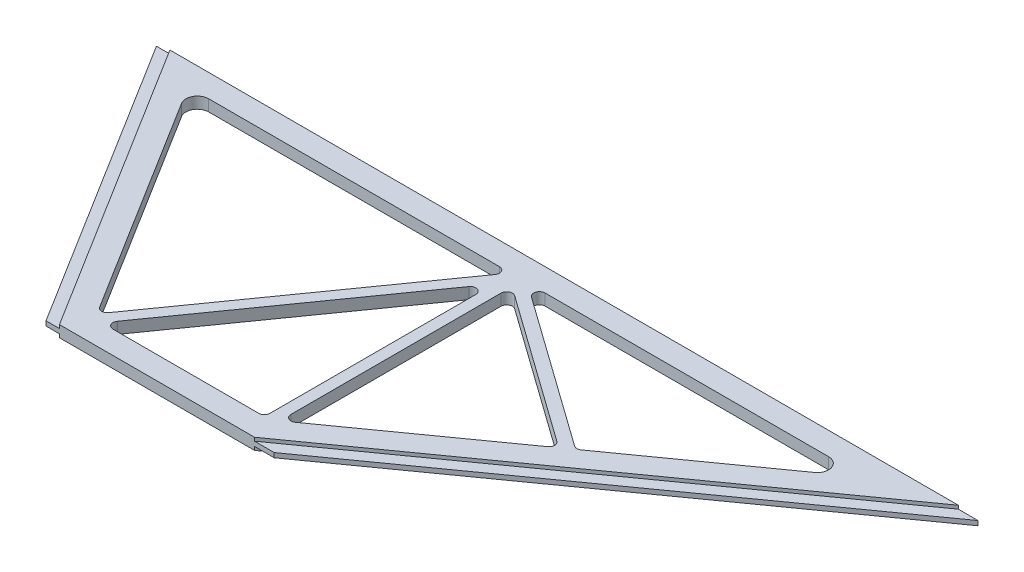
SolidWorks part; units mm, degrees
material "6061-T6 (SS)"
ref_plane "Front Plane" through (0, 0, 0) normal (0, 0, 1) x (1, 0, 0)
ref_plane "Top Plane" through (0, 0, 0) normal (0, 1, 0) x (1, 0, 0)
ref_plane "Right Plane" through (0, 0, 0) normal (1, 0, 0) x (0, 0, -1)
sketch "CS path" plane through (0, 0, 0) normal (0, 1, 0) x (1, 0, 0)
  line L0 (-228.6, 0) -> (228.6, 0)
  line L1 (0, 0) -> (-63.5, -163.068) construction
  line L2 (0, -163.068) -> (228.6, 0)
  line L6 (-127, -163.068) -> (0, -163.068)
  line L9 (-127, -163.068) -> (-228.6, 0) construction
  line L12 (-127, -163.068) -> (-228.6, 0)
  dimension "D1" = 457.2
  dimension "D2" = 127
  dimension "D3" = 163.068
  dimension "D4" = 228.6
extrude "Boss-Extrude1" add sketch "CS path" along normal blind 3.175 and the other way blind 3.175
sketch "Sketch1" plane through (0, 3.175, 0) normal (0, 1, 0) x (1, 0, 0)
  line L0 (-228.6, 0) -> (-127, -163.068)
  line L1 (0, -163.068) -> (228.6, 0)
  line L2 (-228.6, 0) -> (228.6, 0) construction
  line L3 (-127, -163.068) -> (0, -163.068) construction
  line L4 (-221.1183, 0) -> (-119.5183, -163.068)
  line L5 (-10.9346, -163.068) -> (217.6654, 0)
  line L6 (-223.2105, 3.3579) -> (-121.6105, -159.7101) construction
  line L7 (-3.6876, -157.8985) -> (224.9124, 5.1695) construction
  line L8 (-228.6, 0) -> (-221.1183, 0)
  line L9 (-127, -163.068) -> (-119.5183, -163.068)
  line L10 (0, -163.068) -> (-10.9346, -163.068)
  line L11 (217.6654, 0) -> (228.6, 0)
  dimension "D1" = 6.35
extrude "Cut-Extrude1" cut sketch "Sketch1" against normal blind 1.905
mirror "Mirror1" about plane through (0, 0, 0) normal (0, 1, 0) of "Cut-Extrude1"
sketch "Sketch2" plane through (0, 3.175, 0) normal (0, 1, 0) x (1, 0, 0)
  line L0 (-221.1183, 0) -> (217.6654, 0) construction
  line L1 (217.6654, 0) -> (-10.9346, -163.068) construction
  line L2 (-10.9346, -163.068) -> (-119.5183, -163.068) construction
  line L3 (-119.5183, -163.068) -> (-221.1183, 0) construction
  line L4 (-198.2422, -12.7) -> (177.9924, -12.7)
  line L5 (177.9924, -12.7) -> (-15.0001, -150.368)
  line L6 (-15.0001, -150.368) -> (-112.4677, -150.368)
  line L7 (-112.4677, -150.368) -> (-198.2422, -12.7)
  line L8 (-15.0001, -150.368) -> (-15.0001, -12.7) construction
  line L9 (-15.0001, -12.7) -> (-112.4677, -150.368) construction
  line L10 (-15.0001, -12.7) -> (81.4962, -81.534) construction
  line L11 (-15.0001, -150.368) -> (-198.2422, -12.7) construction
  dimension "D1" = 12.7
extrude "Cut-Extrude2" cut sketch "Sketch2" against normal blind 6.35
sketch "Sketch3" plane through (0, 3.175, 0) normal (0, 1, 0) x (1, 0, 0)
  line L0 (-15.0001, -150.368) -> (-15.0001, -12.7) construction
  line L1 (177.9924, -12.7) -> (-198.2422, -12.7) construction
  line L2 (-15.0001, -12.7) -> (81.4962, -81.534) construction
  line L3 (-15.0001, -150.368) -> (177.9924, -12.7) construction
  line L4 (-15.0001, -12.7) -> (-112.4677, -150.368) construction
  line L5 (-18.8903, -12.7) -> (-114.2887, -147.4453)
  line L6 (-11.8251, -148.1032) -> (-11.8251, -18.8648)
  line L7 (-18.8903, -12.7) -> (-9.5328, -12.7)
  line L8 (-18.1751, -22.6792) -> (-108.5776, -150.368)
  line L9 (-18.1751, -150.368) -> (-18.1751, -22.6792)
  line L10 (-9.5328, -12.7) -> (84.2298, -79.584)
  line L11 (-198.2422, -12.7) -> (-112.4677, -150.368) construction
  line L12 (-112.4677, -150.368) -> (-15.0001, -150.368) construction
  line L13 (-15.0001, -150.368) -> (84.2298, -79.584) construction
  line L14 (177.9924, -12.7) -> (-198.2422, -12.7) construction
  line L15 (-17.5914, -10.8654) -> (-115.059, -148.5334) construction
  line L16 (78.7625, -83.484) -> (84.2298, -79.584)
  line L17 (-11.8251, -150.368) -> (-11.8251, -12.7) construction
  line L18 (-11.8251, -148.1032) -> (-15.0001, -150.368)
  line L19 (-13.1563, -10.1152) -> (83.34, -78.9492) construction
  line L20 (-15.0001, -150.368) -> (-18.1751, -150.368)
  line L21 (-11.8251, -18.8648) -> (78.7625, -83.484)
  line L22 (-114.2887, -147.4453) -> (-112.4677, -150.368)
  line L23 (-18.1751, -150.368) -> (-18.1751, -12.7) construction
  line L24 (-112.4677, -150.368) -> (-108.5776, -150.368)
  dimension "D1" = 3.175
  dimension "D2" = 3.175
extrude "Boss-Extrude2" add sketch "Sketch3" against normal blind 6.35
fillet "Fillet1" radius 3.175 10 edges at (84.2298, 0, 79.584) (-114.2887, 0, 147.4453) (-108.5776, 0, 150.368) (-18.1751, 0, 150.368) (-11.8251, 0, 148.1032) (78.7625, 0, 83.484) (-9.5328, 0, 12.7) (-18.8903, 0, 12.7) (-18.1751, 0, 22.6792) (-11.8251, 0, 18.8648)
fillet "Fillet2" radius 6.35 2 edges at (177.9924, 0, 12.7) (-198.2422, 0, 12.7)
